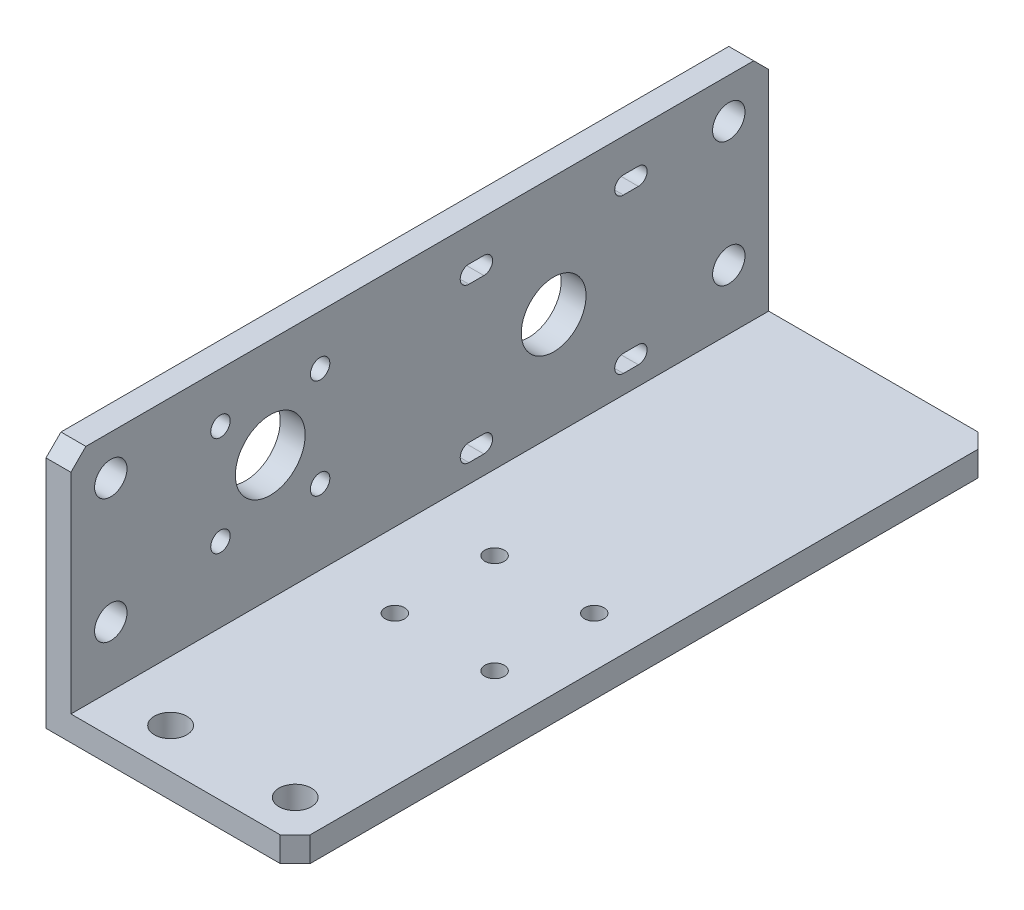
SolidWorks part; units mm, degrees
material "Lega 1060"
ref_plane "Piano frontale" through (0, 0, 0) normal (0, 0, 1) x (1, 0, 0)
ref_plane "Piano superiore" through (0, 0, 0) normal (0, 1, 0) x (1, 0, 0)
ref_plane "Piano destro" through (0, 0, 0) normal (1, 0, 0) x (0, 0, -1)
sketch "Schizzo1" plane through (0, 0, 0) normal (0, 0, 1) x (1, 0, 0)
  line L0 (0, 0) -> (0, 50)
  line L1 (0, 50) -> (5, 50)
  line L2 (5, 50) -> (5, 5)
  line L3 (5, 5) -> (50, 5)
  line L4 (50, 5) -> (50, 0)
  line L5 (50, 0) -> (0, 0)
  dimension "D1" = 5
  dimension "D2" = 5
  dimension "D3" = 50
  dimension "D4" = 50
extrude "Estrusione-Estrusione1" add sketch "Schizzo1" along normal blind 140
sketch "Schizzo2" plane through (0, 0, 0) normal (0, -1, 0) x (1, 0, 0)
  line L0 (5.4524, 132) -> (42.7933, 132) construction
  line L1 (0, 140) -> (50, 140) construction
  line L5 (50, 140) -> (50, 0) construction
  point P4 (17, 132)
  point P5 (42, 132)
  dimension "D1" = 8
  dimension "D2" = 25
  dimension "D3" = 8
sketch "Schizzo3" plane through (0, 0, 0) normal (-1, 0, 0) x (0, 0, 1)
  line L0 (132, 44.621) -> (132, 5.772) construction
  line L1 (140, 50) -> (140, 0) construction
  line L2 (140, 50) -> (0, 50) construction
  point P4 (132, 42)
  point P5 (132, 17)
  dimension "D1" = 8
  dimension "D2" = 8
  dimension "D3" = 25
hole_wizard "Foro Ø6.5 (6.5)-1" positions "Schizzo5" profile "Schizzo4" hole size "Ø6.5" standard "ISO" end condition through all
sketch "Schizzo5" plane through (0, 0, 0) normal (0, -1, 0) x (-1, 0, 0)
  point P0 (-17, -132)
  point P3 (-42, -132)
sketch "Schizzo4" plane through (17, 0, 132) normal (1, 0, 0) x (0, 0, -1)
  line L0 (0, 0) -> (0, 50)
  line L1 (0, 50) -> (3.25, 50)
  line L2 (3.25, 50) -> (3.25, 0)
  line L5 (3.25, 0) -> (0, 0)
  line L11 (0, -6.35) -> (0, 107.95) construction
  dimension "Thru Hole Dia." = 6.5
  dimension "Thru Hole Depth" = 50
hole_wizard "Foro Ø6.5 (6.5)-2" positions "Schizzo7" profile "Schizzo6" hole size "Ø6.5" standard "ISO"
sketch "Schizzo7" plane through (0, 0, 0) normal (-1, 0, 0) x (0, 0, 1)
  point P1 (132, 42)
  point P4 (132, 17)
sketch "Schizzo6" plane through (0, 42, 132) normal (0, 1, 0) x (0, 0, 1)
  line L0 (0, 0) -> (0, 6.9528)
  line L1 (0, 6.9528) -> (3.25, 5)
  line L2 (3.25, 5) -> (3.25, 0)
  line L5 (3.25, 0) -> (0, 0)
  line L10 (0, 6.9528) -> (-3.25, 5) construction
  line L11 (0, -6.35) -> (0, 107.95) construction
  dimension "Hole Dia." = 6.5
  dimension "Hole Depth" = 5
  dimension "Drill Angle" = 118
ref_plane "Piano1" through (0, 0, 70) normal (0, 0, 1) x (1, 0, 0)
mirror "Specchia1" about plane through (0, 0, 70) normal (0, 0, 1) of "Foro Ø6.5 (6.5)-2"
sketch "Schizzo8" plane through (0, 0, 0) normal (0, -1, 0) x (1, 0, 0)
  line L0 (30, 80) -> (7.0316, 80) construction
  line L1 (30, 80) -> (-7.1051, 42.8949) construction
  line L2 (0, 140) -> (50, 140) construction
  line L3 (50, 140) -> (50, 0) construction
  circle A0 centre (20, 70) radius 1.75
  circle A1 centre (20, 90) radius 1.75
  circle A2 centre (40, 90) radius 1.75
  circle A3 centre (40, 70) radius 1.75
  point P18 (30, 80)
  dimension "D3" = 3.5
  dimension "D1" = 60
  dimension "D2" = 20
  dimension "D4" = 45
  dimension "D5" = 20
  dimension "D6" = 4
sketch "Schizzo9" plane through (0, 0, 0) normal (-1, 0, 0) x (0, 0, 1)
  line L2 (140, 50) -> (0, 50) construction
  line L3 (140, 50) -> (140, 0) construction
  circle A4 centre (100, 30) radius 7
  point P18 (100, 30)
  dimension "D7" = 14
  dimension "D1" = 20
  dimension "D2" = 40
extrude "Taglio-Estrusione2" cut sketch "Schizzo9" against normal up to next
sketch "Schizzo11" plane through (0, 0, 0) normal (-1, 0, 0) x (0, 0, 1)
  line L0 (21.2202, 26) -> (65.0608, 26) construction
  line L1 (60.1405, 10.5) -> (57.1405, 10.5) construction
  line L2 (140, 0) -> (0, 0) construction
  line L3 (60.1405, 41.5) -> (57.1405, 41.5) construction
  line L4 (60.1405, 39.75) -> (57.1405, 39.75)
  line L5 (60.1405, 43.25) -> (57.1405, 43.25)
  line L6 (43.1405, 26) -> (43.1405, 48.418) construction
  line L7 (60.1405, 12.25) -> (57.1405, 12.25)
  line L8 (60.1405, 8.75) -> (57.1405, 8.75)
  line L9 (26.1405, 10.5) -> (29.1405, 10.5) construction
  line L10 (26.1405, 12.25) -> (29.1405, 12.25)
  line L11 (26.1405, 8.75) -> (29.1405, 8.75)
  line L12 (26.1405, 41.5) -> (29.1405, 41.5) construction
  line L13 (26.1405, 39.75) -> (29.1405, 39.75)
  line L14 (26.1405, 43.25) -> (29.1405, 43.25)
  circle A0 centre (43.1405, 26) radius 6.5
  arc A1 (60.1405, 39.75) -> (60.1405, 43.25) centre (60.1405, 41.5) ccw
  arc A2 (60.1405, 12.25) -> (60.1405, 8.75) centre (60.1405, 10.5) cw
  arc A3 (57.1405, 8.75) -> (57.1405, 12.25) centre (57.1405, 10.5) cw
  arc A4 (26.1405, 12.25) -> (26.1405, 8.75) centre (26.1405, 10.5) ccw
  arc A5 (29.1405, 8.75) -> (29.1405, 12.25) centre (29.1405, 10.5) ccw
  circle A6 centre (43.1405, 26) radius 21.9203 construction
  arc A7 (57.1405, 43.25) -> (57.1405, 39.75) centre (57.1405, 41.5) ccw
  arc A8 (26.1405, 39.75) -> (26.1405, 43.25) centre (26.1405, 41.5) cw
  arc A9 (29.1405, 43.25) -> (29.1405, 39.75) centre (29.1405, 41.5) cw
  circle A10 centre (100, 30) radius 7 construction
  point P10 (58.6405, 10.5)
  point P13 (58.6405, 41.5)
  point P18 (27.6405, 10.5)
  point P20 (43.1405, 26)
  point P33 (27.6405, 41.5)
  dimension "D2" = 31
  dimension "D3" = 31
  dimension "D5" = 57
  dimension "D1" = 13
  dimension "D4" = 26
  dimension "D8" = 3.5
  dimension "D9" = 3
extrude "Taglio-Estrusione4" cut sketch "Schizzo11" against normal up to next
chamfer "Smusso1" distance 3 angle 45 4 edges at (50, 2.5, 0) (2.5, 50, 0) (2.5, 50, 140) (50, 2.5, 140)
sketch "Sketch4" plane through (0, 0, 0) normal (-1, 0, 0) x (0, 0, 1)
  line L0 (100, 30) -> (100, 45.3374) construction
  line L1 (100, 30) -> (85.4455, 44.5545) construction
  line L2 (100, 30) -> (85.4455, 30) construction
  point P3 (90, 40)
  point P5 (110, 40)
  point P6 (90, 20)
  point P8 (110, 20)
  dimension "D1" = 45
  dimension "D2" = 10
hole_wizard "M3.5 Clearance Hole1" positions "3DSketch3" profile "Sketch5" hole size "M3.5" standard "ISO" end condition through all
sketch3d "3DSketch3"
  point P0 (0, 40, 90)
  point P3 (0, 40, 110)
  point P6 (0, 20, 110)
  point P9 (0, 20, 90)
sketch "Sketch5" plane through (0, 40, 90) normal (0, 1, 0) x (0, 0, 1)
  line L0 (0, 0) -> (0, 50)
  line L1 (0, 50) -> (1.95, 50)
  line L2 (1.95, 50) -> (1.95, 0)
  line L5 (1.95, 0) -> (0, 0)
  line L11 (0, -6.35) -> (0, 107.95) construction
  dimension "Thru Hole Dia." = 3.9
  dimension "Thru Hole Depth" = 50
hole_wizard "M3.5 Clearance Hole2" positions "3DSketch4" profile "Sketch6" hole size "M3.5" standard "ISO" end condition through all
sketch3d "3DSketch4"
  point P0 (20, 0, 90)
  point P3 (40, 0, 90)
  point P6 (40, 0, 70)
  point P9 (20, 0, 70)
sketch "Sketch6" plane through (20, 0, 90) normal (1, 0, 0) x (0, 0, -1)
  line L0 (0, 0) -> (0, 50)
  line L1 (0, 50) -> (1.95, 50)
  line L2 (1.95, 50) -> (1.95, 0)
  line L5 (1.95, 0) -> (0, 0)
  line L11 (0, -6.35) -> (0, 107.95) construction
  dimension "Thru Hole Dia." = 3.9
  dimension "Thru Hole Depth" = 50
sketch "Sketch7" plane through (0, 0, 0) normal (0, -1, 0) x (1, 0, 0)
  line L0 (0, 140) -> (47, 140) construction
  line L1 (0, 140) -> (0, 0) construction
  point P0 (5, 140)
  dimension "D1" = 5
